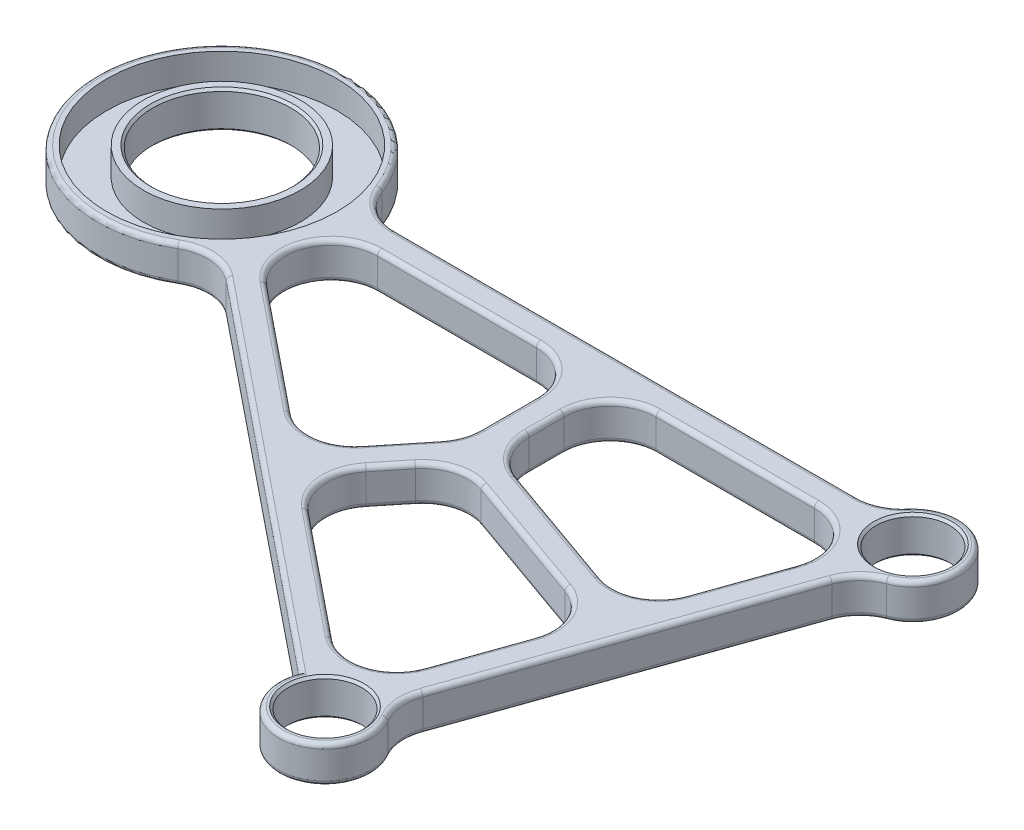
SolidWorks part; units mm, degrees
ref_plane "Plan de face" through (0, 0, 0) normal (0, 0, 1) x (1, 0, 0)
ref_plane "Plan de dessus" through (0, 0, 0) normal (0, 1, 0) x (1, 0, 0)
ref_plane "Plan de droite" through (0, 0, 0) normal (1, 0, 0) x (0, 0, -1)
sketch "Esquisse1" plane through (0, 0, 0) normal (0, 1, 0) x (1, 0, 0)
  line L0 (-42.1372, 14.8978) -> (16.1961, -32.2427) construction
  line L1 (16.1961, -32.2427) -> (32.8628, 14.8978) construction
  line L2 (32.8628, 14.8978) -> (-42.1372, 14.8978) construction
  line L3 (-28.7208, 16.3978) -> (28.0931, 16.3978)
  line L4 (-28.7208, 13.3978) -> (-1.5, 13.3978)
  line L5 (29.8587, 10.9008) -> (23.6152, -6.7583)
  line L6 (19.2002, -28.2458) -> (32.6871, 9.9008)
  line L8 (13.4292, -28.0781) -> (-7.2544, -11.3633)
  line L9 (0, 0) -> (0, 14.8978) construction
  line L10 (0, 0) -> (24.5294, -8.6725) construction
  line L11 (0, 0) -> (-9.3638, -11.5871) construction
  line L12 (-7.2544, -11.3633) -> (0.5, -1.7678)
  line L19 (0.5, -1.7678) -> (22.6152, -9.5867)
  line L20 (23.6152, -6.7583) -> (1.5, 1.0607)
  line L21 (-1.5, 13.3978) -> (-1.5, 0.5303)
  line L22 (1.5, 13.3978) -> (1.5, 1.0607)
  line L23 (-1.5, 0.5303) -> (-9.5877, -9.4777)
  line L24 (1.5, 13.3978) -> (28.0931, 13.3978)
  line L25 (22.6152, -9.5867) -> (16.3718, -27.2458)
  line L26 (-9.5877, -9.4777) -> (-30.7594, 7.6317)
  line L28 (-32.645, 5.2983) -> (11.5435, -30.4114)
  circle A1 centre (32.8628, 14.8978) radius 4
  circle A2 centre (16.1961, -32.2427) radius 4
  arc A4 (28.0931, 13.3978) -> (29.8587, 10.9008) centre (32.8628, 14.8978) ccw
  arc A5 (11.5435, -30.4114) -> (19.2002, -28.2458) centre (16.1961, -32.2427) ccw
  arc A8 (32.6871, 9.9008) -> (28.0931, 16.3978) centre (32.8628, 14.8978) ccw
  arc A9 (16.3718, -27.2458) -> (13.4292, -28.0781) centre (16.1961, -32.2427) ccw
  arc A10 (-30.7594, 7.6317) -> (-28.7208, 13.3978) centre (-42.1372, 14.8978) ccw
  arc A11 (-28.7208, 16.3978) -> (-32.645, 5.2983) centre (-42.1372, 14.8978) ccw
  point P29 (24.5294, -8.6725)
  dimension "D5" = 8
  dimension "D2" = 13.5
  dimension "D3" = 1
  dimension "D7" = 3
  dimension "D8" = 1.5
  dimension "D11" = 1.5
  dimension "D12" = 3
  dimension "D6" = 75
  dimension "D14" = 75
  dimension "D15" = 50
  dimension "D16" = 3
  dimension "D17" = 3
  dimension "D13" = 3
  dimension "D4" = 3
extrude "Boss.-Extru.1" add sketch "Esquisse1" along normal blind 4
sketch "Esquisse2" plane through (0, 4, 0) normal (0, 1, 0) x (1, 0, 0)
  circle A0 centre (-42.1372, 14.8978) radius 12.5
  arc A1 (-28.7208, 16.3978) -> (-32.645, 5.2983) centre (-42.1372, 14.8978) ccw construction
  circle A2 centre (-42.1372, 14.8978) radius 8.5
  dimension "D1" = 1
  dimension "D2" = 17
extrude "Enlèv. mat.-Extru.1" cut sketch "Esquisse2" against normal offset from surface (3 mm away) 1 up to face at (16.8743, 0, -6.3721)
sketch "Esquisse3" plane through (0, 4, 0) normal (0, 1, 0) x (1, 0, 0)
  circle A0 centre (-42.1372, 14.8978) radius 7.5
  dimension "D1" = 15
extrude "Enlèv. mat.-Extru.2" cut sketch "Esquisse3" against normal up to surface (4 mm away) up to face at (16.8743, 0, -6.3721)
fillet "Congé1" radius 5 20 edges at (28.0931, 2, -16.3978) (32.6871, 2, -9.9008) (19.2002, 2, 28.2458) (0.5, 2, 1.7678) (-7.2544, 2, 11.3633) (22.6152, 2, 9.5867) (13.4292, 2, 28.0781) (16.3718, 2, 27.2458) (29.8587, 2, -10.9008) (23.6152, 2, 6.7583) (1.5, 2, -13.3978) (1.5, 2, -1.0607) (-1.5, 2, -0.5303) (-9.5877, 2, 9.4777) (-1.5, 2, -13.3978) (28.0931, 2, -13.3978) (-32.645, 2, -5.2983) (-28.7208, 2, -16.3978) (-28.7208, 2, -13.3978) (-30.7594, 2, -7.6317)
fillet "Congé2" radius 5 3 edges at (-29.4006, 2, -10.3947) (14.8236, 2, 27.3901) (28.7452, 2, -11.9862)
fillet "Congé3" radius 0.5 70 edges at (27.7529, 4, -11.2845) (26.8332, 4, -2.3434) (22.7227, 4, 4.8894) (11.8673, 4, 2.6047) (2.4175, 4, -1.7094) (1.5, 4, -6.497) (2.9645, 4, -11.9333) (20.7464, 4, 10.4792) (19.3973, 4, 18.6884) (14.4928, 4, 26.2206) (3.3119, 4, 19.9021) (-5.1948, 4, 11.1447) (-2.9169, 4, 5.996) (0.8058, 4, 2.8491) (-2.9645, 4, -11.9333) (-1.5, 4, -5.3479) (-1.786, 4, -0.6314) (-4.528, 4, 3.2167) (-9.8062, 4, 7.4182) (-20.1859, 4, 0.9131) (-28.4665, 4, -10.0644) (16.5668, 0, 37.2289) (19.8785, 0, 27.7028) (25.9437, 0, 9.1725) (32.8734, 0, -9.0522) (36.9453, 0, -17.7845) (27.3551, 0, -16.8563) (-9.0325, 0, 13.7835) (-32.3826, 0, -3.942) (-54.8651, 0, -19.3978) (-27.6642, 0, -17.2878) (16.5668, 4, 37.2289) (19.8785, 4, 27.7028) (25.9437, 4, 9.1725) (32.8734, 4, -9.0522) (36.9453, 4, -17.7845) (27.3551, 4, -16.8563) (-9.0325, 4, 13.7835) (-32.3826, 4, -3.942) (-54.8651, 4, -19.3978) (-27.6642, 4, -17.2878) (15.0852, 4, -13.3978) (10.8673, 4, 5.4331) (-15.1262, 4, -13.3978) (0.2234, 0, -16.3978) (0.2234, 4, -16.3978) (-5.1948, 0, 11.1447) (-2.9169, 0, 5.996) (0.8058, 0, 2.8491) (10.8673, 0, 5.4331) (20.7464, 0, 10.4792) (19.3973, 0, 18.6884) (14.4928, 0, 26.2206) (-28.4665, 0, -10.0644) (-15.1262, 0, -13.3978) (-2.9645, 0, -11.9333) (-1.5, 0, -5.3479) (-1.786, 0, -0.6314) (-4.528, 0, 3.2167) (-9.8062, 0, 7.4182) (2.4175, 0, -1.7094) (1.5, 0, -6.497) (2.9645, 0, -11.9333) (15.0852, 0, -13.3978) (27.7529, 0, -11.2845) (26.8332, 0, -2.3434) (22.7227, 0, 4.8894) (3.3119, 0, 19.9021) (-20.1859, 0, 0.9131) (11.8673, 0, 2.6047)
chamfer "Chanfrein1" distance 0.25 angle 45 6 edges at (16.1961, 0, 36.2427) (32.8628, 0, -10.8978) (32.8628, 4, -10.8978) (-42.1372, 0, -7.3978) (-42.1372, 4, -7.3978) (16.1961, 4, 36.2427)
equation "\"D11@Esquisse1\"=\"D7@Esquisse1\"/2"
equation "\"D12@Esquisse1\"=\"D7@Esquisse1\""
equation "\"D8@Esquisse1\"=\"D7@Esquisse1\"/2"
equation "\"D16@Esquisse1\"=\"D7@Esquisse1\""
equation "\"D17@Esquisse1\"=\"D13@Esquisse1\""
equation "\"D13@Esquisse1\"=\"D7@Esquisse1\""
